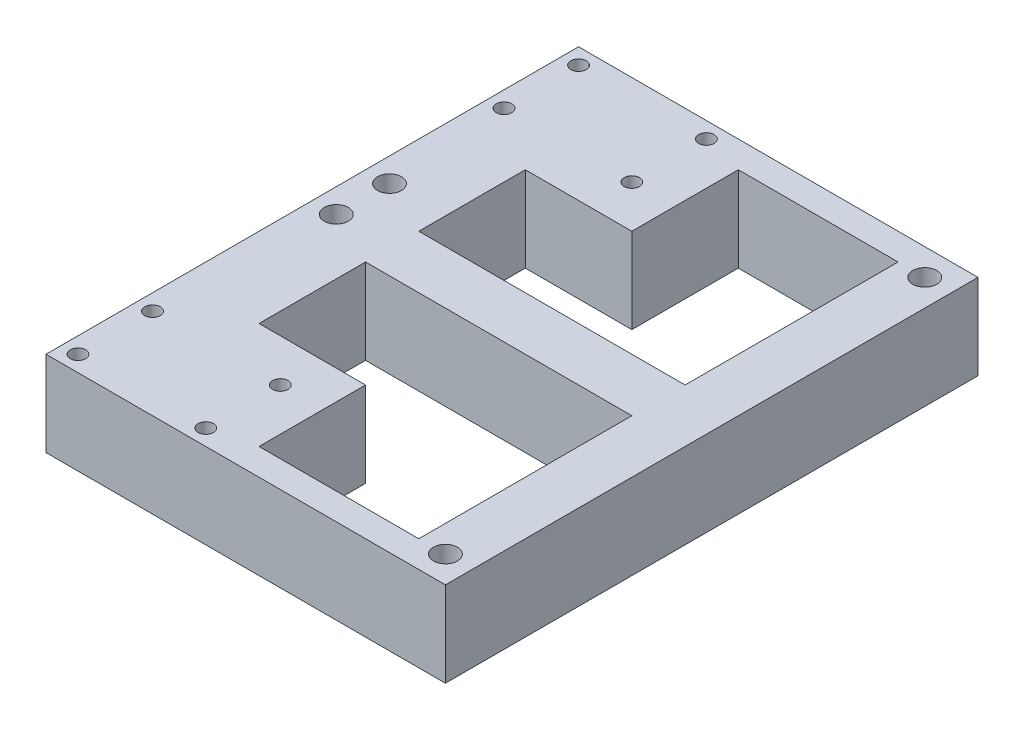
SolidWorks part; units mm, degrees
ref_plane "前视基准面" through (0, 0, 0) normal (0, 0, 1) x (1, 0, 0)
ref_plane "上视基准面" through (0, 0, 0) normal (0, 1, 0) x (1, 0, 0)
ref_plane "右视基准面" through (0, 0, 0) normal (1, 0, 0) x (0, 0, -1)
other "Configuration Table"
sketch "草图1" plane through (0, 0, 0) normal (0, 1, 0) x (1, 0, 0)
  line L1 (0, 0) -> (-75, 0)
  line L2 (0, 0) -> (0, 100)
  line L3 (0, 100) -> (-75, 100)
  line L4 (-75, 0) -> (-75, 100)
  dimension "D1" = 100
  dimension "D2" = 75
extrude "凸台-拉伸1" add sketch "草图1" along normal blind 16
sketch "草图6" plane through (0, 16, 0) normal (0, 1, 0) x (1, 0, 0)
  line L0 (-75, 100) -> (-75, 0) construction
  line L1 (-40, 45) -> (-5, 45)
  line L2 (-40, 25) -> (-40, 5)
  line L3 (-40, 5) -> (-5, 5)
  line L4 (-5, 45) -> (-5, 5)
  line L5 (0, 0) -> (0, 100) construction
  line L6 (-75, 0) -> (0, 0) construction
  line L7 (-75, 50) -> (-60.5255, 50) construction
  line L8 (-40, 95) -> (-5, 95)
  line L9 (-5, 55) -> (-5, 95)
  line L10 (-40, 55) -> (-5, 55)
  line L11 (-40, 75) -> (-40, 95)
  line L12 (-40, 75) -> (-70, 75)
  line L13 (-40, 45) -> (-70, 45)
  line L15 (-40, 25) -> (-70, 25)
  line L16 (-70, 45) -> (-70, 25)
  line L17 (-40, 55) -> (-70, 55)
  line L18 (-70, 55) -> (-70, 75)
  dimension "D1" = 35
  dimension "D2" = 5
  dimension "D3" = 5
  dimension "D4" = 40
  dimension "D5" = 30
  dimension "D6" = 20
extrude "切除-拉伸5" cut sketch "草图6" against normal up to next
sketch "草图8" plane through (0, 16, 0) normal (0, 1, 0) x (1, 0, 0)
  line L0 (-75, 100) -> (-72, 100) construction
  line L1 (0, 100) -> (-75, 100) construction
  line L2 (-72, 100) -> (-72, 97) construction
  line L3 (-72, 97) -> (-48, 97) construction
  line L4 (-48, 97) -> (-48, 83) construction
  line L5 (-48, 83) -> (-72, 83) construction
  line L6 (-75, 50) -> (-51.1245, 50) construction
  line L7 (-75, 100) -> (-75, 0) construction
  line L8 (-48, 17) -> (-72, 17) construction
  line L9 (-48, 3) -> (-48, 17) construction
  line L10 (-72, 3) -> (-48, 3) construction
  line L11 (-72, 0) -> (-72, 3) construction
  line L12 (-75, 0) -> (-72, 0) construction
  circle A0 centre (-72, 97) radius 1.45
  circle A1 centre (-72, 83) radius 1.45
  circle A2 centre (-48, 97) radius 1.45
  circle A3 centre (-48, 83) radius 1.45
  circle A4 centre (-48, 17) radius 1.45
  circle A5 centre (-48, 3) radius 1.45
  circle A6 centre (-72, 17) radius 1.45
  circle A7 centre (-72, 3) radius 1.45
  dimension "D6" = 2.9
  dimension "D7" = 2.9
  dimension "D8" = 2.9
  dimension "D9" = 2.9
  dimension "D1" = 3
  dimension "D2" = 3
  dimension "D3" = 24
  dimension "D4" = 14
  dimension "D5" = 24
extrude "切除-拉伸7" cut sketch "草图8" against normal through all
sketch "草图9" plane through (-5, 0, 0) normal (-1, 0, 0) x (0, 0, 1)
  line L0 (-45, 0) -> (-5, 0) construction
  line L1 (-5, 0) -> (-5, 16) construction
  line L2 (-5, 16) -> (-45, 16) construction
  line L3 (-45, 16) -> (-45, 0) construction
  line L4 (-95, 0) -> (-55, 0) construction
  line L5 (-55, 0) -> (-55, 16) construction
  line L6 (-55, 16) -> (-95, 16) construction
  line L7 (-95, 16) -> (-95, 0) construction
  line L8 (-45, 0) -> (-5, 0)
  line L9 (-5, 0) -> (-5, 16)
  line L10 (-5, 16) -> (-45, 16)
  line L11 (-45, 16) -> (-45, 0)
  line L12 (-95, 0) -> (-55, 0)
  line L13 (-55, 0) -> (-55, 16)
  line L14 (-55, 16) -> (-95, 16)
  line L15 (-95, 16) -> (-95, 0)
extrude "凸台-拉伸2" add sketch "草图9" along normal blind 5
sketch "草图10" plane through (0, 16, 0) normal (0, 1, 0) x (1, 0, 0)
  line L0 (0, 100) -> (0, 95) construction
  line L1 (0, 0) -> (0, 100) construction
  line L2 (0, 95) -> (-5, 95) construction
  line L3 (0, 50) -> (-16.1785, 50) construction
  circle A0 centre (-5, 95) radius 2.25
  circle A1 centre (-5, 5) radius 2.25
  dimension "D3" = 4.5
  dimension "D1" = 5
  dimension "D2" = 5
extrude "切除-拉伸8" cut sketch "草图10" against normal blind 5
sketch "草图11" plane through (0, 0, 0) normal (0, -1, 0) x (1, 0, 0)
  circle A0 centre (-5, -95) radius 2.25 construction
  circle A1 centre (-5, -5) radius 2.25 construction
  circle A2 centre (-5, -95) radius 2.25
  circle A3 centre (-5, -5) radius 2.25
extrude "切除-拉伸9" cut sketch "草图11" against normal blind 5
sketch "草图12" plane through (-70, 0, 0) normal (1, 0, 0) x (0, 0, -1)
  line L0 (25, 0) -> (45, 0) construction
  line L1 (45, 0) -> (45, 16) construction
  line L2 (45, 16) -> (25, 16) construction
  line L3 (25, 16) -> (25, 0) construction
  line L4 (55, 0) -> (75, 0) construction
  line L5 (75, 0) -> (75, 16) construction
  line L6 (75, 16) -> (55, 16) construction
  line L7 (55, 16) -> (55, 0) construction
  line L8 (25, 0) -> (45, 0)
  line L9 (45, 0) -> (45, 16)
  line L10 (45, 16) -> (25, 16)
  line L11 (25, 16) -> (25, 0)
  line L12 (55, 0) -> (75, 0)
  line L13 (75, 0) -> (75, 16)
  line L14 (75, 16) -> (55, 16)
  line L15 (55, 16) -> (55, 0)
extrude "凸台-拉伸3" add sketch "草图12" along normal blind 10
sketch "草图13" plane through (0, 16, 0) normal (0, 1, 0) x (1, 0, 0)
  line L0 (-75, 50) -> (-70.5, 50) construction
  line L1 (-75, 100) -> (-75, 0) construction
  line L3 (-70.5, 50) -> (-70.5, 60) construction
  circle A0 centre (-70.5, 50) radius 2.25
  circle A1 centre (-70.5, 60) radius 2.25
  dimension "D4" = 4.5
  dimension "D5" = 4.5
  dimension "D3" = 10
  dimension "D6" = 4.5
  dimension "D1" = 4.5
  dimension "D2" = 10
extrude "切除-拉伸10" cut sketch "草图13" against normal blind 5
